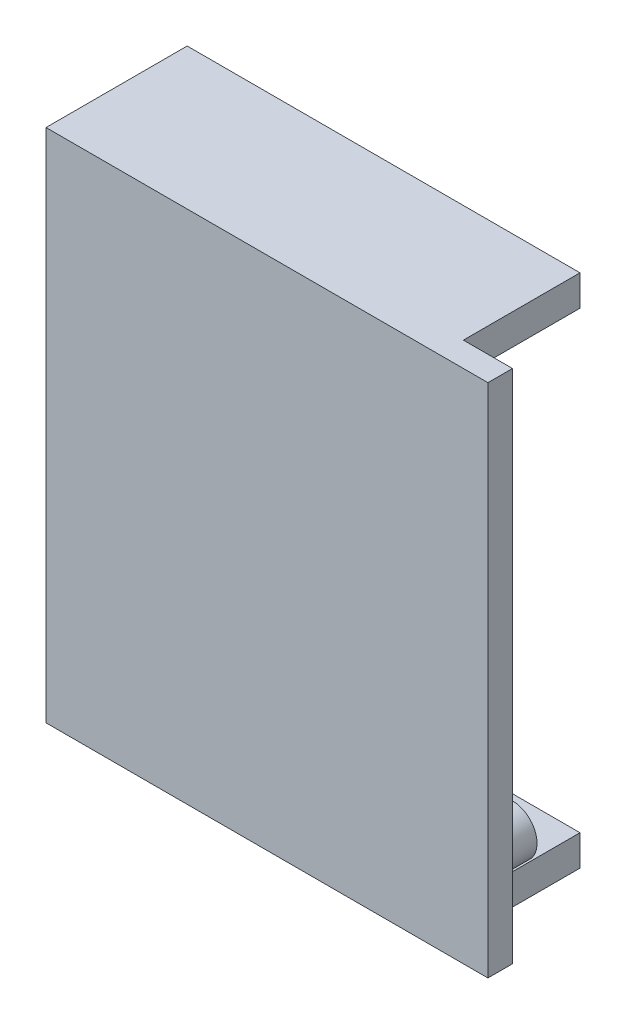
SolidWorks part; units mm, degrees
ref_plane "前视基准面" through (0, 0, 0) normal (0, 0, 1) x (1, 0, 0)
ref_plane "上视基准面" through (0, 0, 0) normal (0, 1, 0) x (1, 0, 0)
ref_plane "右视基准面" through (0, 0, 0) normal (1, 0, 0) x (0, 0, -1)
sketch "草图1" plane through (0, 0, 0) normal (0, 0, 1) x (1, 0, 0)
  line L0 (-21, -16.4) -> (-21, 16.4) construction
  line L1 (-21, -21) -> (15, -21)
  line L2 (-21, -21) -> (-21, 21)
  line L3 (-21, 21) -> (15, 21)
  line L4 (15, -21) -> (15, 21)
  line L5 (12, -17.5) -> (-12, -17.5) construction
  line L6 (-12, 17.5) -> (12, 17.5) construction
  line L7 (13, 16.5) -> (13, -16.5) construction
  dimension "D1" = 3.5
  dimension "D2" = 3.5
  dimension "D3" = 2
extrude "凸台-拉伸1" add sketch "草图1" along normal blind 2
sketch "草图2" plane through (0, 0, 0) normal (0, 0, -1) x (-1, 0, 0)
  line L0 (21, 0) -> (-15, 0) construction
  line L1 (21, 21) -> (-11, 21)
  line L2 (21, 21) -> (21, 18.5)
  line L3 (21, 18.5) -> (-11, 18.5)
  line L4 (-11, 21) -> (-11, 18.5)
  line L5 (21, 21) -> (21, -21) construction
  line L6 (-15, -21) -> (-15, 21) construction
  line L7 (-13, 16.5) -> (-13, 5) construction
  line L8 (21, -18.5) -> (-11, -18.5)
  line L9 (-11, -21) -> (-11, -18.5)
  line L10 (21, -21) -> (-11, -21)
  line L11 (21, -21) -> (21, -18.5)
  dimension "D1" = 2
  dimension "D2" = 2.5
extrude "凸台-拉伸2" add sketch "草图2" along normal blind 9.5
sketch "草图3" plane through (0, 0, 0) normal (0, 0, -1) x (-1, 0, 0)
  line L0 (-11, -18.5) -> (-11, -21) construction
  line L1 (-14, 19.75) -> (-11, 19.75)
  line L2 (-14, 19.75) -> (-14, -19.75)
  line L3 (-14, -19.75) -> (-11, -19.75)
  line L4 (-11, 19.75) -> (-11, -19.75)
  line L5 (-11, 21) -> (-11, 18.5) construction
  line L6 (-15, -21) -> (-15, 21) construction
  point P6 (0, 0)
  point P9 (-11, 19.75)
  dimension "D1" = 1
extrude "切除-拉伸1" cut sketch "草图3" against normal blind 1
sketch "草图4" plane through (0, 0, 0) normal (0, 0, -1) x (-1, 0, 0)
  circle A0 centre (11, 15.5) radius 2
  circle A1 centre (-11, -15.5) radius 2
  circle A2 centre (11, 15.5) radius 1.1
  circle A3 centre (-11, -15.5) radius 1.1
  dimension "D1" = 4
  dimension "D2" = 2.2
extrude "凸台-拉伸3" add sketch "草图4" along normal blind 4
extrude "凸台-拉伸4" add sketch "草图4<2>" against normal up to surface (1 mm away) contours A1 up to face at (12.5, 0, 1)
sketch "草图4<2>" plane through (0, 0, 0) normal (0, 0, -1) x (-1, 0, 0) same geometry as "草图4"
sketch "草图5" plane through (0, 0, 0) normal (0, 0, -1) x (-1, 0, 0)
  line L0 (9, 15.5) -> (9, 18.5)
  line L1 (-11, 18.5) -> (21, 18.5) construction
  line L2 (9, 18.5) -> (13, 18.5)
  line L3 (13, 18.5) -> (13, 15.5)
  line L4 (13, 16.4) -> (13, -16.4) construction
  line L5 (13, 15.5) -> (11, 17.5)
  line L6 (11, 17.5) -> (9, 15.5)
  line L7 (11, 17.5) -> (11, 18.5) construction
  circle A0 centre (11, 15.5) radius 2 construction
extrude "凸台-拉伸5" add sketch "草图5" along normal up to surface (4 mm away) up to face at (-13, 15.5, -4)
sketch "草图6" plane through (0, 0, 0) normal (0, 0, -1) x (-1, 0, 0)
  line L0 (-11, -17.5) -> (-11, -18.5)
  line L1 (-11, -17.5) -> (-9, -15.5)
  line L2 (-9, -15.5) -> (-9, -18.5)
  line L3 (21, -18.5) -> (-11, -18.5) construction
  line L4 (-9, -18.5) -> (-11, -18.5)
  circle A0 centre (-11, -15.5) radius 2 construction
extrude "凸台-拉伸6" add sketch "草图6" along normal up to surface (4 mm away) up to face at (9, -15.5, -4)
sketch "草图8" plane through (0, 0, 0) normal (0, 0, -1) x (-1, 0, 0)
  line L0 (7.5, 12.5) -> (-7.5, -12.5) construction
  line L1 (-7.5, 12.5) -> (7.5, 12.5) construction
  line L2 (-7.5, 12.5) -> (-7.5, -12.5) construction
  line L3 (-7.5, -12.5) -> (7.5, -12.5) construction
  line L4 (7.5, 12.5) -> (7.5, -12.5) construction
  circle A0 centre (7.5, -12.5) radius 2.5
  circle A1 centre (-7.5, 12.5) radius 2.5
  point P4 (0, 0)
  dimension "D3" = 5
  dimension "D1" = 25
  dimension "D2" = 15
extrude "凸台-拉伸7" add sketch "草图8" along normal blind 4
sketch "草图9" plane through (-21, 0, 0) normal (-1, 0, 0) x (0, 0, 1)
  line L0 (0, 18.5) -> (0, -18.5) construction
  line L1 (-9.5, -18.5) -> (0, -18.5)
  line L2 (-9.5, -18.5) -> (-9.5, -17)
  line L3 (-9.5, -17) -> (0, -17)
  line L4 (0, -18.5) -> (0, -17)
  line L5 (0, 0) -> (-15.888, 0) construction
  line L6 (-9.5, 17) -> (0, 17)
  line L7 (0, 18.5) -> (0, 17)
  line L8 (-9.5, 18.5) -> (0, 18.5)
  line L9 (-9.5, 18.5) -> (-9.5, 17)
  dimension "D1" = 1.5
extrude "凸台-拉伸8" add sketch "草图9" against normal blind 4
